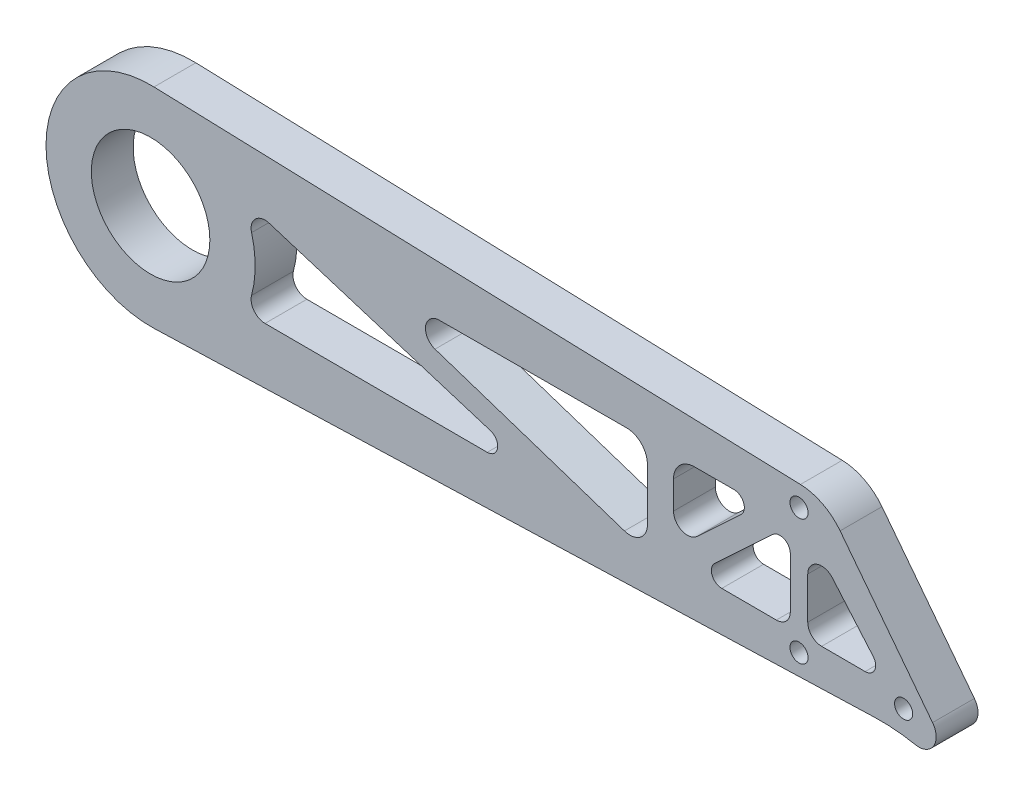
SolidWorks part; units mm, degrees
material "Thornel Mat VMA"
ref_plane "前视基准面" through (0, 0, 0) normal (0, 0, 1) x (1, 0, 0)
ref_plane "上视基准面" through (0, 0, 0) normal (0, 1, 0) x (1, 0, 0)
ref_plane "右视基准面" through (0, 0, 0) normal (1, 0, 0) x (0, 0, -1)
sketch "草图1" plane through (0, 0, 0) normal (0, 0, 1) x (1, 0, 0)
  line L0 (0.9754, 29.9841) -> (231.0289, 22.5)
  line L1 (0.9754, -29.9841) -> (231.0289, -22.5)
  line L2 (0, 0) -> (270, 0) construction
  line L3 (186, 18) -> (186, -18) construction
  line L4 (186, -18) -> (216, -16.9524) construction
  arc A0 (0.9754, 29.9841) -> (0.9754, -29.9841) centre (0, 0) ccw
  arc A1 (231.0289, -22.5) -> (231.0289, 22.5) centre (270, 0) ccw
  circle A2 centre (186, 18) radius 2.6
  circle A3 centre (186, -18) radius 2.6
  circle A4 centre (216, -16.9524) radius 2.6
  point P10 (186, 0)
  dimension "D1" = 60
  dimension "D2" = 90
  dimension "D7" = 5.2
  dimension "D3" = 270
  dimension "D4" = 45
  dimension "D5" = 84
  dimension "D6" = 36
  dimension "D8" = 88
  dimension "D9" = 30
extrude "凸台-拉伸1" add sketch "草图1" along normal blind 12
sketch "草图2" plane through (0, 0, 12) normal (0, 0, 1) x (1, 0, 0)
  circle A0 centre (0, 0) radius 17
  dimension "D1" = 34
extrude "切除-拉伸1" cut sketch "草图2" against normal through all
sketch "草图3" plane through (0, 0, 12) normal (0, 0, 1) x (1, 0, 0)
  circle A0 centre (0, 0) radius 19 construction
  circle A1 centre (-19, 0) radius 1.6
  circle A2 centre (-9.5, 16.4545) radius 1.6
  circle A3 centre (9.5, 16.4545) radius 1.6
  circle A4 centre (19, 0) radius 1.6
  circle A5 centre (9.5, -16.4545) radius 1.6
  circle A6 centre (-9.5, -16.4545) radius 1.6
  dimension "D1" = 38
  dimension "D2" = 3.2
  dimension "D3" = 6
extrude "切除-拉伸2" [suppressed] cut sketch "草图3" against normal through all
fillet "圆角1" radius 50 2 edges at (231.0289, -22.5, 6) (231.0289, 22.5, 6)
sketch "草图6" plane through (0, 0, 0) normal (0, 0, -1) x (-1, 0, 0)
  circle A0 centre (-270, 0) radius 40 construction
  circle A1 centre (-230, 0) radius 2.1
  circle A2 centre (-235.359, -20) radius 2.1
  circle A3 centre (-250, -34.641) radius 2.1
  circle A4 centre (-270, -40) radius 2.1
  circle A5 centre (-290, -34.641) radius 2.1
  circle A6 centre (-304.641, -20) radius 2.1
  circle A7 centre (-310, 0) radius 2.1
  circle A8 centre (-304.641, 20) radius 2.1
  circle A9 centre (-290, 34.641) radius 2.1
  circle A10 centre (-270, 40) radius 2.1
  circle A11 centre (-250, 34.641) radius 2.1
  circle A12 centre (-235.359, 20) radius 2.1
  dimension "D1" = 80
  dimension "D2" = 4.2
  dimension "D3" = 12
extrude "切除-拉伸5" [suppressed] cut sketch "草图6" against normal through all
sketch "草图7" plane through (0, 0, 12) normal (0, 0, 1) x (1, 0, 0)
  circle A0 centre (270, 0) radius 21
  dimension "D1" = 42
extrude "切除-拉伸6" cut sketch "草图7" against normal through all
sketch "草图8" plane through (0, 0, 12) normal (0, 0, 1) x (1, 0, 0)
  line L0 (42.8917, 13.6126) -> (124.8483, -10.9463)
  line L1 (124.8483, -10.9463) -> (42.8917, -13.6126)
  line L8 (164.8483, -10.6456) -> (221.1834, 10.8139)
  line L9 (164.8483, -10.6456) -> (220.7851, -8.8258)
  line L11 (0.9754, -29.9841) -> (207.8537, -23.2539) construction
  line L12 (207.8537, 23.2539) -> (0.9754, 29.9841) construction
  line L13 (82.8906, 13.3119) -> (128.8906, 11.8154)
  line L14 (128.8906, 11.8154) -> (138.8483, -9.4904)
  line L15 (138.8483, -9.4904) -> (82.8906, 13.3119)
  line L16 (181.1834, 10.1142) -> (150.8483, -9.1)
  line L17 (150.8483, -9.1) -> (143.8826, 11.3276)
  line L18 (143.8826, 11.3276) -> (181.1834, 10.1142)
  line L19 (0, 0) -> (270, 0) construction
  line L20 (135, 0) -> (135, -176.2302) construction
  arc A0 (42.8917, 13.6126) -> (42.8917, -13.6126) centre (0, 0) cw
  arc A1 (221.1834, 10.8139) -> (220.7851, -8.8258) centre (270, 0) ccw
  dimension "D1" = 50
  dimension "D2" = 45
  dimension "D3" = 15
  dimension "D4" = 15
  dimension "D5" = 12
  dimension "D6" = 14
  dimension "D7" = 40
  dimension "D8" = 14
  dimension "D9" = 40
  dimension "D10" = 14
  dimension "D11" = 15
  dimension "D12" = 12
  dimension "D13" = 16
  dimension "D14" = 16
  dimension "D15" = 82
  dimension "D16" = 46
  dimension "D17" = 14
extrude "切除-拉伸7" [suppressed] cut sketch "草图8" against normal through all
fillet "5" [suppressed] radius 5
fillet "1.5" [suppressed] radius 1.5
fillet "3" [suppressed] radius 3
fillet "圆角5" [suppressed] radius 3
fillet "1" [suppressed] radius 1
fillet "4" [suppressed] radius 4
sketch "草图9" plane through (0, 0, 12) normal (0, 0, 1) x (1, 0, 0)
  line L0 (315, 0) -> (298.0206, -35.2115)
  arc A0 (241.3324, -34.6867) -> (241.3324, 34.6867) centre (270, 0) ccw construction
  arc A1 (298.0206, -35.2115) -> (315, 0) centre (270, 0) ccw
extrude "切除-拉伸8" [suppressed] cut sketch "草图9" against normal through all
sketch "草图11" plane through (0, 0, 0) normal (0, 0, -1) x (-1, 0, 0)
  circle A0 centre (0, 0) radius 17 construction
  arc A1 (3.4814, 16.6397) -> (-3.4814, 16.6397) centre (0, 0) ccw
  arc A2 (-3.4814, 16.6397) -> (3.4814, 16.6397) centre (0, 17) ccw
  arc A3 (14.7495, 8.453) -> (16.9011, 1.8309) centre (16.168, 5.2533) ccw
  arc A4 (12.5971, -11.4155) -> (6.9641, -15.5081) centre (9.9923, -13.7533) ccw
  arc A5 (-6.9641, -15.5081) -> (-12.5971, -11.4155) centre (-9.9923, -13.7533) ccw
  arc A6 (-16.9011, 1.8309) -> (-14.7495, 8.453) centre (-16.168, 5.2533) ccw
  arc A7 (-14.7495, 8.453) -> (-16.9011, 1.8309) centre (0, 0) ccw
  arc A8 (-12.5971, -11.4155) -> (-6.9641, -15.5081) centre (0, 0) ccw
  arc A9 (16.9011, 1.8309) -> (14.7495, 8.453) centre (0, 0) ccw
  arc A10 (6.9641, -15.5081) -> (12.5971, -11.4155) centre (0, 0) ccw
  dimension "D1" = 7
  dimension "D2" = 5
extrude "凸台-拉伸2" [suppressed] add sketch "草图11" against normal up to surface (15 mm away)
fillet "圆角10" [suppressed] radius 2
sketch "草图12" plane through (0, 0, 0) normal (0, 0, -1) x (-1, 0, 0)
  line L0 (-234.5782, 12.3792) -> (-173.777, 14.3572) construction
  line L1 (-270, 0) -> (-118.7673, 0) construction
  line L2 (-234.5782, -12.3792) -> (-173.777, -14.3572) construction
  line L3 (-207.8537, 23.2539) -> (-0.9754, 29.9841) construction
  circle A0 centre (-270, 0) radius 60 construction
  circle A1 centre (-211.4546, 13.1315) radius 2.1
  dimension "D1" = 120
  dimension "D3" = 4.2
  dimension "D2" = 10
extrude "切除-拉伸9" [suppressed] cut sketch "草图12" against normal through all
sketch "草图13" plane through (0, 0, 0) normal (0, 0, -1) x (-1, 0, 0)
  line L0 (-270, 0) -> (-186.8718, 0) construction
  circle A0 centre (-211.4546, -13.1315) radius 2.1
  circle A1 centre (-211.4546, 13.1315) radius 2.1
  circle A2 centre (-211.4546, 13.1315) radius 2.1 construction
  dimension "D1" = 0
extrude "切除-拉伸10" [suppressed] cut sketch "草图13" against normal through all
sketch "草图14" plane through (0, 0, 0) normal (0, 0, -1) x (-1, 0, 0)
  line L0 (-270, 0) -> (-182.3944, 0) construction
  circle A0 centre (-270, 0) radius 60 construction
  circle A1 centre (-210, 0) radius 2.1
  dimension "D1" = 120
  dimension "D2" = 4.2
extrude "切除-拉伸11" [suppressed] cut sketch "草图14" against normal through all
pattern_linear "阵列(线性)1" [suppressed] count 3 spacing 15 along (-0.9995, 0.0325, 0)
pattern_linear "阵列(线性)2" [suppressed] count 3 spacing 15 along (-0.9995, -0.0325, 0)
sketch "草图15" plane through (0, 0, 0) normal (0, 0, -1) x (-1, 0, 0)
  circle A0 centre (-270, 0) radius 48
  dimension "D1" = 96
extrude "切除-拉伸12" cut sketch "草图15" against normal through all
sketch "草图16" plane through (0, 0, 0) normal (0, 0, -1) x (-1, 0, 0)
  line L3 (-222, 0) -> (-50222, 0) construction
  arc A0 (-231.1251, -28.1557) -> (-231.1251, 28.1557) centre (-270, 0) ccw construction
  arc A2 (-222, 0) -> (-231.1251, 28.1557) centre (-270, 0) ccw
  arc A3 (-231.1251, 28.1557) -> (-207.8537, 23.2539) centre (-209.4795, 73.2275) ccw construction
  arc A4 (-231.1251, 28.1557) -> (-215.7827, 23.6264) centre (-209.4795, 73.2275) ccw
  arc A5 (-215.7827, 23.6264) -> (-222, 0) centre (-174, 0) ccw
  dimension "D1" = 96
extrude "切除-拉伸13" cut sketch "草图16" against normal through all
sketch "草图17" plane through (0, 0, 0) normal (0, 0, -1) x (-1, 0, 0)
  line L0 (-186, 18) -> (-216, -16.9524) construction
  line L1 (-146, 19.263) -> (-186, 18) construction
  line L2 (-186, -18) -> (-186, 18) construction
  line L9 (-207.8537, 23.2539) -> (-0.9754, 29.9841) construction
  line L10 (-195.5353, 5.3553) -> (-207.2498, -8.2931)
  line L11 (-204.9662, -13.247) -> (-192.4905, -13.2173)
  line L13 (-146, 19.263) -> (36.6057, 9.693) construction
  line L14 (0, 0) -> (-257.2871, 0) construction
  line L15 (-146, -19.263) -> (36.6057, -9.693) construction
  line L22 (-186, -18) -> (-146, -19.263) construction
  line L24 (-146, 19.263) -> (-146, -19.263) construction
  line L37 (-186, 18) -> (-146, -19.263) construction
  line L39 (-0.9754, -29.9841) -> (-207.8537, -23.2539) construction
  line L40 (-183.5, 5.3596) -> (-183.5, -9.1862)
  line L42 (-161.8075, -7.9538) -> (-178.4551, 7.5547)
  line L43 (-167.3045, 13.1572) -> (-155.9857, 13.1302)
  line L52 (-150, 7.1302) -> (-150, -0.8769)
  line L53 (-210.8447, 13.261) -> (-202.0751, 13.2401)
  line L54 (-199.0494, 6.6349) -> (-212.9476, -9.5576)
  line L55 (-216, -16.9524) -> (-186, -18) construction
  line L58 (-163.8453, -13.1489) -> (-179.4905, -13.1862)
  line L59 (-188.5, -9.2173) -> (-188.5, 2.7501)
  line L65 (-156.7265, -3.8037) -> (-169.3565, 7.9621)
  line L66 (-142.5, 7.0836) -> (-142.5, -8.086)
  line L67 (-135.9286, -12.8327) -> (-81.5845, 5.1583)
  line L68 (-82.8321, 12.9556) -> (-136.4857, 13.0836)
  line L69 (-96.5619, -12.9884) -> (-32.8221, -12.8363)
  line L70 (-97.462, -7.1244) -> (-34.0223, 12.655)
  line L72 (-207.8537, 23.2539) -> (-0.9754, 29.9841) construction
  arc A3 (-215.7827, 23.6264) -> (-222, 0) centre (-174, 0) ccw construction
  arc A4 (-215.7827, 23.6264) -> (-222, 0) centre (-174, 0) ccw construction
  arc A6 (-231.1251, -28.1557) -> (-222, 0) centre (-270, 0) ccw construction
  arc A7 (-231.1251, -28.1557) -> (-222, 0) centre (-270, 0) ccw construction
  arc A20 (-214.7336, 10.2359) -> (-216, 0) centre (-174, 0) ccw
  arc A21 (-215.9897, -10.9524) -> (-213.8989, -11.3323) centre (-216, -16.9524) ccw
  arc A54 (-210.5599, 20.6731) -> (-216, 0) centre (-174, 0) ccw construction
  arc A56 (-28.9691, -7.7967) -> (-28.9691, 7.7967) centre (0, 0) cw
  arc A57 (-212.9476, -9.5576) -> (-215.9897, -10.9524) centre (-215.9829, -6.9524) cw
  arc A59 (-216.4638, -7.0624) -> (-216, 0) centre (-270, 0) ccw
  arc A62 (-188.5, -9.2173) -> (-192.4905, -13.2173) centre (-192.5, -9.2173) cw
  arc A64 (-199.0494, 6.6349) -> (-202.0751, 13.2401) centre (-202.0846, 9.2401) ccw
  arc A66 (-213.8989, -11.3323) -> (-216.4638, -7.0624) centre (-212.4982, -7.5856) cw
  arc A68 (-207.2498, -8.2931) -> (-204.9662, -13.247) centre (-204.9734, -10.247) ccw
  arc A69 (-210.8447, 13.261) -> (-214.7336, 10.2359) centre (-210.8542, 9.2611) ccw
  arc A72 (-195.5353, 5.3553) -> (-188.5, 2.7501) centre (-192.5, 2.7501) cw
  arc A79 (-179.4905, -13.1862) -> (-183.5, -9.1862) centre (-179.5, -9.1862) cw
  arc A81 (-167.3045, 13.1572) -> (-169.3565, 7.9621) centre (-167.3116, 10.1572) ccw
  arc A82 (-183.5, 5.3596) -> (-178.4551, 7.5547) centre (-180.5, 5.3596) cw
  arc A86 (-163.8453, -13.1489) -> (-161.8075, -7.9538) centre (-163.8524, -10.1489) ccw
  arc A87 (-142.5, -8.086) -> (-135.9286, -12.8327) centre (-137.5, -8.086) ccw
  arc A88 (-150, -0.8769) -> (-156.7265, -3.8037) centre (-154, -0.8769) cw
  arc A91 (-81.5845, 5.1583) -> (-82.8321, 12.9556) centre (-82.8416, 8.9556) ccw
  arc A92 (-32.8221, -12.8363) -> (-28.9691, -7.7967) centre (-32.8317, -8.8363) ccw
  arc A93 (-28.9691, 7.7967) -> (-34.0223, 12.655) centre (-32.8317, 8.8363) ccw
  arc A94 (-142.5, 7.0836) -> (-136.4857, 13.0836) centre (-136.5, 7.0836) cw
  arc A95 (-155.9857, 13.1302) -> (-150, 7.1302) centre (-156, 7.1302) cw
  circle A97 centre (-146, -19.263) radius 11.5 construction
  arc A98 (-97.462, -7.1244) -> (-96.5619, -12.9884) centre (-96.5691, -9.9884) ccw
  point P99 (-116.4221, -13.0358)
  point P111 (-142.5, 13.098)
  dimension "D4" = 6
  dimension "D5" = 6
  dimension "D6" = 6
  dimension "D8" = 2.5
  dimension "D9" = 1
  dimension "D10" = 2.5
  dimension "D7" = 4
  dimension "D11" = 10
  dimension "D12" = 3
  dimension "D20" = 2.5
  dimension "D21" = 10
  dimension "D22" = 2
  dimension "D23" = 54
  dimension "D24" = 4
  dimension "D18" = 3.5
  dimension "D29" = 5
  dimension "D30" = 4
  dimension "D31" = 3
  dimension "D36" = 3
  dimension "D37" = 4
  dimension "D38" = 23
  dimension "D39" = 30
  dimension "D40" = 6
  dimension "D41" = 4
  dimension "D42" = 4
  dimension "D43" = 4
  dimension "D44" = 6
  dimension "D19" = 2
  dimension "D26" = 3
  dimension "D25" = 4
  dimension "D13" = 3
  dimension "D14" = 6
  dimension "D15" = 40
  dimension "D16" = 2.5
  dimension "D17" = 4
  dimension "D45" = 7
extrude "切除-拉伸14" cut sketch "草图17" against normal through all
sketch "草图19" plane through (0, 0, 0) normal (1, 0, 0) x (0, 0, -1)
  line L1 (0, 0) -> (9.577, 0)
  line L2 (0, 0) -> (0, -9.1022)
  line L3 (0, -9.1022) -> (9.577, -9.1022)
  line L4 (9.577, 0) -> (9.577, -9.1022)
extrude "凸台-拉伸3" add sketch "草图19" along normal blind 1 separate body
delete or keep bodies "实体-删除/保留 1" type delete bodies bodies 132
sketch "草图21" plane through (0, 0, 12) normal (0, 0, 1) x (1, 0, 0)
  line L2 (216, -16.9524) -> (186, 18) construction
  line L3 (225.347, -17.6099) -> (193.4715, 23.7218)
  line L6 (207.8537, 23.2539) -> (0.9754, 29.9841) construction
  line L7 (207.8537, 23.2539) -> (193.4715, 23.7218)
  arc A8 (222, 0) -> (231.1251, -28.1557) centre (270, 0) ccw construction
  arc A9 (207.8537, 23.2539) -> (215.7827, 23.6264) centre (209.4795, 73.2275) ccw construction
  arc A10 (222, 0) -> (215.7827, 23.6264) centre (174, 0) ccw construction
  arc A11 (207.8537, 23.2539) -> (215.7827, 23.6264) centre (209.4795, 73.2275) ccw
  arc A12 (222, 0) -> (215.7827, 23.6264) centre (174, 0) ccw
  arc A13 (222, 0) -> (225.347, -17.6099) centre (270, 0) ccw
  dimension "D1" = 3
  dimension "D2" = 7
extrude "切除-拉伸16" cut sketch "草图21" against normal through all
fillet "圆角11" radius 5 1 edges at (231.1251, -28.1557, 6)
fillet "圆角12" radius 15 1 edges at (193.4715, 23.7218, 6)
fillet "圆角13" radius 5 1 edges at (225.347, -17.6099, 6)
move or copy body "实体-移动/复制1" [suppressed] bodies to move or copy 137
